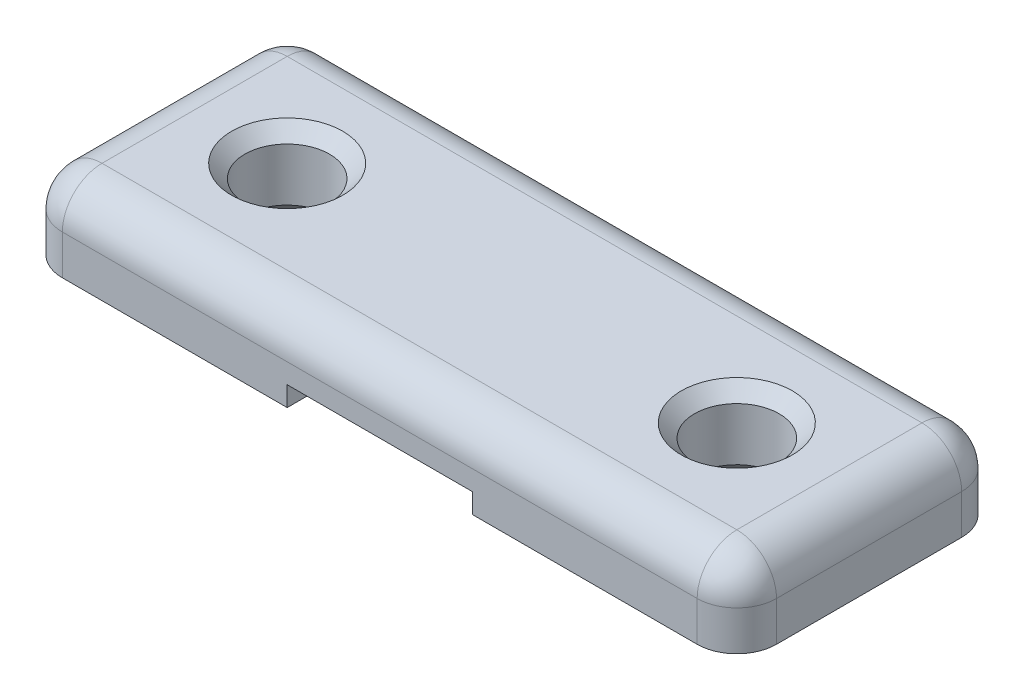
SolidWorks part; units mm, degrees
ref_plane "Спереди" through (0, 0, 0) normal (0, 0, 1) x (1, 0, 0)
ref_plane "Сверху" through (0, 0, 0) normal (0, 1, 0) x (1, 0, 0)
ref_plane "Справа" through (0, 0, 0) normal (1, 0, 0) x (0, 0, -1)
sketch "Эскиз1" plane through (0, 0, 0) normal (0, 1, 0) x (1, 0, 0)
  line L0 (-25.7727, 0) -> (59.6455, 0) construction
  line L1 (-13.5, -5) -> (13.5, -5)
  line L2 (-13.5, -5) -> (-13.5, 5)
  line L3 (-13.5, 5) -> (13.5, 5)
  line L4 (13.5, -5) -> (13.5, 5)
  line L5 (-13.5, -5) -> (13.5, 5) construction
  line L6 (-13.5, 5) -> (13.5, -5) construction
  circle A0 centre (-8.5, 0) radius 1.6
  circle A1 centre (8.5, 0) radius 1.6
  point P0 (0, 0)
  dimension "D5" = 3.2
  dimension "D1" = 27
  dimension "D2" = 10
  dimension "D3" = 5
  dimension "D4" = 5
extrude "Бобышка-Вытянуть1" add sketch "Эскиз1" along normal blind 3
sketch "Эскиз2" plane through (0, 0, 0) normal (1, 0, 0) x (0, 0, -1)
  line L0 (0, 3.442) -> (0, -0.9238) construction
  line L1 (-5, 0) -> (5, 0) construction
  line L2 (-2.1549, 0.75) -> (1.4366, 0.75) construction
  line L3 (-4.7433, 0.75) -> (-5, 0.75)
  line L4 (-5, 3) -> (-5, 0) construction
  line L5 (-3.2567, 0.75) -> (-2.7433, 0.75)
  line L6 (-1.2567, 0.75) -> (-0.7433, 0.75)
  line L7 (0.7433, 0.75) -> (1.2567, 0.75)
  line L8 (2.7433, 0.75) -> (3.2567, 0.75)
  line L9 (4.7433, 0.75) -> (5, 0.75)
  line L10 (5, 3) -> (5, 0) construction
  line L11 (5, 0.75) -> (5, 0)
  line L12 (5, 0) -> (-5, 0)
  line L13 (-5, 0) -> (-5, 0.75)
  arc A0 (-0.5051, 0.3182) -> (0.5051, 0.3182) centre (0, 0.56) ccw
  arc A1 (-0.5946, 0.6196) -> (-0.5051, 0.3182) centre (0.3969, 0.75) ccw
  arc A2 (0.5051, 0.3182) -> (0.5946, 0.6196) centre (-0.3969, 0.75) ccw
  arc A3 (-0.5946, 0.6196) -> (-0.7433, 0.75) centre (-0.7433, 0.6) ccw
  arc A4 (0.7433, 0.75) -> (0.5946, 0.6196) centre (0.7433, 0.6) ccw
  arc A5 (1.4054, 0.6196) -> (1.2567, 0.75) centre (1.2567, 0.6) ccw
  arc A6 (1.4054, 0.6196) -> (1.4949, 0.3182) centre (2.3969, 0.75) ccw
  arc A7 (1.4949, 0.3182) -> (2.5051, 0.3182) centre (2, 0.56) ccw
  arc A8 (2.5051, 0.3182) -> (2.5946, 0.6196) centre (1.6031, 0.75) ccw
  arc A9 (2.7433, 0.75) -> (2.5946, 0.6196) centre (2.7433, 0.6) ccw
  arc A10 (3.4054, 0.6196) -> (3.2567, 0.75) centre (3.2567, 0.6) ccw
  arc A11 (3.4054, 0.6196) -> (3.4949, 0.3182) centre (4.3969, 0.75) ccw
  arc A12 (3.4949, 0.3182) -> (4.5051, 0.3182) centre (4, 0.56) ccw
  arc A13 (4.5051, 0.3182) -> (4.5946, 0.6196) centre (3.6031, 0.75) ccw
  arc A14 (4.7433, 0.75) -> (4.5946, 0.6196) centre (4.7433, 0.6) ccw
  arc A15 (-2.5946, 0.6196) -> (-2.7433, 0.75) centre (-2.7433, 0.6) ccw
  arc A16 (-2.5946, 0.6196) -> (-2.5051, 0.3182) centre (-1.6031, 0.75) ccw
  arc A17 (-2.5051, 0.3182) -> (-1.4949, 0.3182) centre (-2, 0.56) ccw
  arc A18 (-1.4949, 0.3182) -> (-1.4054, 0.6196) centre (-2.3969, 0.75) ccw
  arc A19 (-1.2567, 0.75) -> (-1.4054, 0.6196) centre (-1.2567, 0.6) ccw
  arc A20 (-4.5946, 0.6196) -> (-4.7433, 0.75) centre (-4.7433, 0.6) ccw
  arc A21 (-4.5946, 0.6196) -> (-4.5051, 0.3182) centre (-3.6031, 0.75) ccw
  arc A22 (-4.5051, 0.3182) -> (-3.4949, 0.3182) centre (-4, 0.56) ccw
  arc A23 (-3.4949, 0.3182) -> (-3.4054, 0.6196) centre (-4.3969, 0.75) ccw
  arc A24 (-3.2567, 0.75) -> (-3.4054, 0.6196) centre (-3.2567, 0.6) ccw
  dimension "D1" = 1.12
  dimension "D3" = 2
  dimension "D4" = 3
  dimension "D5" = 0.3
  dimension "D2" = 0.75
  dimension "D6" = 3
extrude "Вырез-Вытянуть1" cut sketch "Эскиз2" against normal mid plane 7 contours L5 A24 A23 A22 L12 A17 A16 A15 | A22 A21 A20 L3 L13 L12 | L6 A19 A18 A17 L12 A0 A1 A3 | A7 A6 A5 L7 A4 A2 A0 L12 | A12 A11 A10 L8 A9 A8 A7 L12 | L9 A14 A13 A12 L12 L11 region at (0, 0.3218, 4.7259) region at (0, 0.3218, -4.7259) region at (0, 0.3218, -3) region at (0, 0.3218, -1) region at (0, 0.3218, 1) region at (0, 0.3218, 3)
fillet "Скругление1" radius 1.5 8 edges at (-13.5, 1.5, -5) (-13.5, 1.5, 5) (13.5, 1.5, 5) (13.5, 1.5, -5) (13.5, 3, 0) (0, 3, 5) (-13.5, 3, 0) (0, 3, -5)
chamfer "Фаска1" distance 0.5 angle 45 4 edges at (8.5, 3, 1.6) (-8.5, 3, 1.6) (-8.5, 0, 1.6) (8.5, 0, 1.6)
